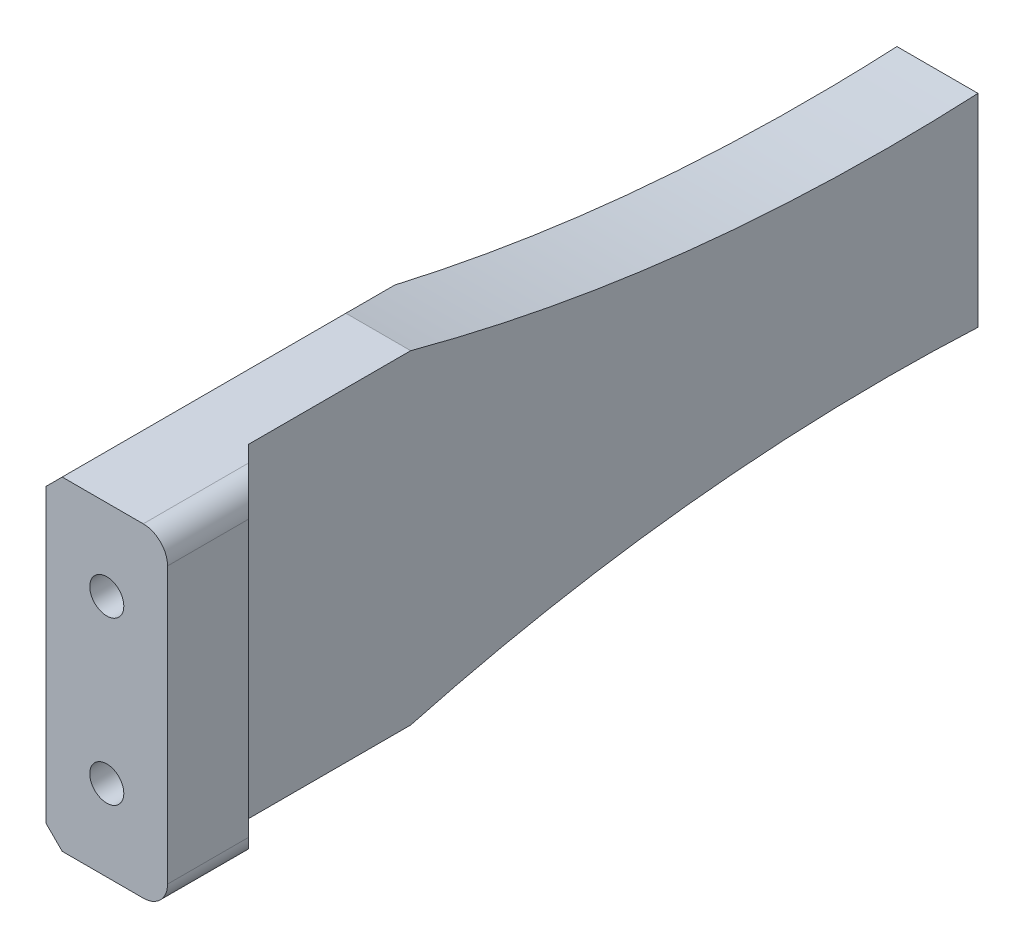
SolidWorks part; units mm, degrees
material "6061 Alloy"
ref_plane "Front Plane" through (0, 0, 0) normal (0, 0, 1) x (1, 0, 0)
ref_plane "Top Plane" through (0, 0, 0) normal (0, 1, 0) x (1, 0, 0)
ref_plane "Right Plane" through (0, 0, 0) normal (1, 0, 0) x (0, 0, -1)
sketch "Sketch1" plane through (0, 0, 0) normal (0, 1, 0) x (1, 0, 0)
  line L0 (0, 0) -> (15, 0)
  line L1 (15, 0) -> (15, 10)
  line L2 (15, 10) -> (10, 10)
  line L3 (10, 10) -> (10, 105)
  line L4 (10, 105) -> (0, 105)
  line L5 (0, 105) -> (0, 0)
  dimension "D1" = 10
  dimension "D2" = 105
  dimension "D3" = 10
  dimension "D4" = 15
extrude "Boss-Extrude1" add sketch "Sketch1" along normal mid plane 40
sketch "Sketch3" plane through (0, 0, 0) normal (-1, 0, 0) x (0, 0, 1)
  line L0 (-105, -20) -> (0, -20) construction
  line L1 (-35, -20) -> (-105, -20)
  line L2 (-105, -20) -> (-105, -12.5)
  line L3 (-105, 20) -> (-105, -20) construction
  spline S0 degree 2 poles (-105, -12.5) (-69.4764, -10.7523) (-35, -20) knots 0 0 0 1 1 1
  dimension "D1" = 7.5
  dimension "D2" = 70
  dimension "D3" = 7
  dimension "D4" = 30
extrude "Cut-Extrude1" cut sketch "Sketch3" against normal through all
mirror "Mirror1" about plane through (0, 0, 0) normal (0, 1, 0) of "Cut-Extrude1"
fillet "Fillet2" radius 3 2 edges at (15, -20, -5) (15, 20, -5)
hole_wizard "M5 Tapped Hole1" positions "Sketch4" profile "Sketch5" tap size "M5" standard "ISO"
sketch "Sketch4" plane through (0, 0, -105) normal (0, 0, -1) x (-1, 0, 0)
  line L1 (0, 12.5) -> (0, -12.5) construction
  line L2 (-10, 12.5) -> (-10, -12.5) construction
  point P0 (-5.195, 0)
  point P9 (0, 0)
  dimension "D1" = 4.805
sketch "Sketch5" plane through (5.195, 0, -105) normal (1, 0, 0) x (0, 1, 0)
  line L0 (0, 0) -> (0, 15)
  line L1 (0, 15) -> (2.1, 13.7382)
  line L2 (2.1, 13.7382) -> (2.1, 0)
  line L5 (2.1, 0) -> (0, 0)
  line L10 (0, 15) -> (-2.1, 13.7382) construction
  line L11 (0, -6.35) -> (0, 107.95) construction
  dimension "Tap Drill Dia." = 4.2
  dimension "Tap Drill Depth" = 15
  dimension "Drill Angle" = 118
hole_wizard "M5 Tapped Hole2" positions "Sketch6" profile "Sketch7" tap size "M5" standard "ISO"
sketch "Sketch6" plane through (0, 0, 0) normal (0, 0, 1) x (1, 0, 0)
  line L0 (15, 17) -> (15, -17) construction
  point P0 (7.5, -10)
  point P2 (7.5, 10)
  point P10 (15, 0)
  dimension "D1" = 20
  dimension "D2" = 10
  dimension "D3" = 7.5
sketch "Sketch7" plane through (7.5, -10, 0) normal (1, 0, 0) x (0, -1, 0)
  line L0 (0, 0) -> (0, 15)
  line L1 (0, 15) -> (2.1, 13.7382)
  line L2 (2.1, 13.7382) -> (2.1, 0)
  line L5 (2.1, 0) -> (0, 0)
  line L10 (0, 15) -> (-2.1, 13.7382) construction
  line L11 (0, -6.35) -> (0, 107.95) construction
  dimension "Tap Drill Dia." = 4.2
  dimension "Tap Drill Depth" = 15
  dimension "Drill Angle" = 118
chamfer "Chamfer1" distance 5 angle 45 1 edges at (10, 0, -10)
chamfer "Chamfer2" distance 2 angle 45 2 edges at (0, -20, -17.5) (0, 20, -17.5)
